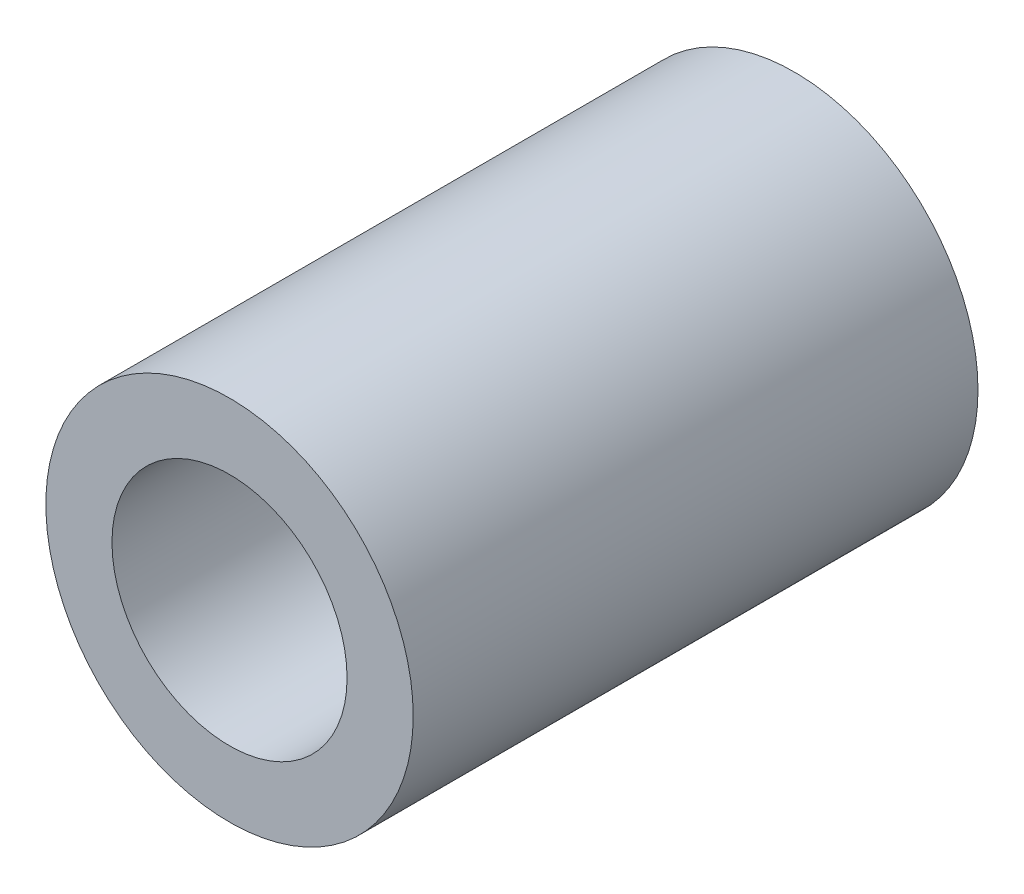
SolidWorks part; units mm, degrees
material "ABS"
ref_plane "Front Plane" through (0, 0, 0) normal (0, 0, 1) x (1, 0, 0)
ref_plane "Top Plane" through (0, 0, 0) normal (0, 1, 0) x (1, 0, 0)
ref_plane "Right Plane" through (0, 0, 0) normal (1, 0, 0) x (0, 0, -1)
sketch "Sketch1" plane through (0, 0, 0) normal (0, 0, 1) x (1, 0, 0)
  circle A0 centre (0, 0) radius 5
  dimension "D1" = 10
extrude "Boss-Extrude1" add sketch "Sketch1" along normal mid plane 15.375
hole_wizard "M6 Clearance Hole1" positions "Sketch2" profile "Sketch3" hole size "M6" standard "ANSI Metric" end condition through all
sketch "Sketch2" plane through (0, 0, 7.6875) normal (0, 0, 1) x (1, 0, 0)
  point P0 (0, 0)
sketch "Sketch3" plane through (0, 0, 7.6875) normal (1, 0, 0) x (0, -1, 0)
  line L0 (0, 0) -> (0, 15.375)
  line L1 (0, 15.375) -> (3.2, 15.375)
  line L2 (3.2, 15.375) -> (3.2, 0)
  line L5 (3.2, 0) -> (0, 0)
  line L11 (0, -6.35) -> (0, 107.95) construction
  dimension "Thru Hole Dia." = 6.4
  dimension "Thru Hole Depth" = 15.375
